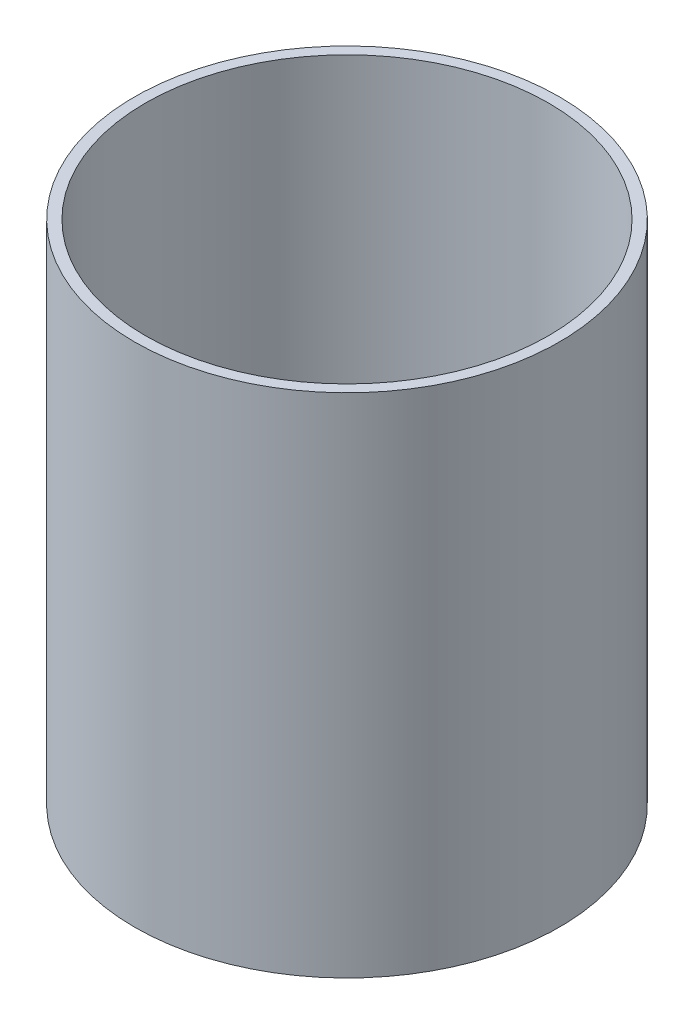
SolidWorks part; units mm, degrees
material "PVC Rigid"
ref_plane "Front Plane" through (0, 0, 0) normal (0, 0, 1) x (1, 0, 0)
ref_plane "Top Plane" through (0, 0, 0) normal (0, 1, 0) x (1, 0, 0)
ref_plane "Right Plane" through (0, 0, 0) normal (1, 0, 0) x (0, 0, -1)
sketch "Sketch1" plane through (0, 0, 0) normal (0, 1, 0) x (1, 0, 0)
  circle A0 centre (0, 0) radius 93.6625
  circle A1 centre (0, 0) radius 88.9
  dimension "D1" = 187.325
  dimension "D2" = 177.8
extrude "Boss-Extrude1" add sketch "Sketch1" along normal mid plane 223.52
